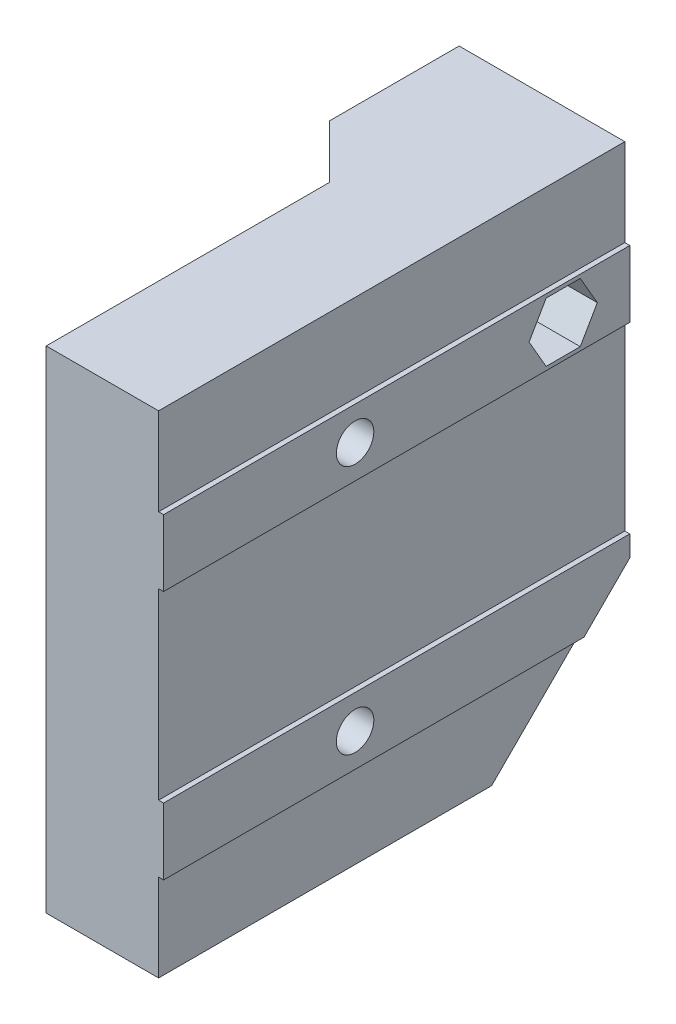
SolidWorks part; units mm, degrees
material "3D printed plastic"
ref_plane "Front Plane" through (0, 0, 0) normal (0, 0, 1) x (1, 0, 0)
ref_plane "Top Plane" through (0, 0, 0) normal (0, 1, 0) x (1, 0, 0)
ref_plane "Right Plane" through (0, 0, 0) normal (1, 0, 0) x (0, 0, -1)
sketch "Sketch1" plane through (0, 0, 0) normal (0, 0, 1) x (1, 0, 0)
  line L0 (0, 0) -> (15, 0) construction
  line L1 (-14, 32.5) -> (-1.5, 32.5)
  line L2 (-14, 32.5) -> (-14, -24.5)
  line L3 (-14, -24.5) -> (-1.5, -24.5)
  line L4 (15, 33.5) -> (15, 23)
  line L5 (1.5, -25.5) -> (15, -25.5)
  line L6 (1.5, -5.8095) -> (1.5, -25.5)
  line L7 (-1.5, 32.5) -> (-1.5, 5.8095)
  line L8 (15, -15) -> (15, -25.5)
  line L9 (1.5, 33.5) -> (1.5, 5.8095)
  line L10 (1.5, 33.5) -> (15, 33.5)
  line L11 (-1.5, -5.8095) -> (-1.5, -24.5)
  line L12 (-1.5, 5.8095) -> (1.5, 5.8095) construction
  line L13 (15, 23) -> (15.6, 23)
  line L14 (15.6, 19) -> (15, 19) construction
  line L15 (15, 15) -> (15.6, 15)
  line L16 (15.6, 23) -> (15.6, 15)
  line L17 (15, -7) -> (15.6, -7)
  line L18 (15, 15) -> (15, -7)
  line L19 (15, -15) -> (15.6, -15)
  line L20 (15.6, -7) -> (15.6, -15)
  line L21 (15.6, -11) -> (16.2538, -11) construction
  arc A0 (1.5, -5.8095) -> (1.5, 5.8095) centre (0, 0) ccw
  arc A1 (-1.5, 5.8095) -> (-1.5, -5.8095) centre (0, 0) ccw
  dimension "D1" = 59
  dimension "D2" = 12
  dimension "D3" = 15
  dimension "D4" = 29
  dimension "D5" = 3
  dimension "D6" = 8
  dimension "D7" = 30
  dimension "D8" = 0.6
  dimension "D9" = 25.5
  dimension "D10" = 1
  dimension "D11" = 1
extrude "Boss-Extrude1" add sketch "Sketch1" along normal mid plane 20
hole_wizard "CBORE for M5 Hex Socket Head Cap Screw1" positions "Sketch3" profile "Sketch2" counterbore size "M5" standard "DIN" end condition through all
sketch "Sketch3" plane through (-14, 0, 0) normal (-1, 0, 0) x (0, 0, 1)
  line L0 (0, 19) -> (0, -11) construction
  line L2 (0, 4) -> (-10, 4) construction
  line L3 (-10, 32.5) -> (-10, -24.5) construction
  line L5 (0, 4) -> (10, 4) construction
  line L7 (10, 32.5) -> (10, -24.5) construction
  point P0 (0, -11)
  point P2 (0, 19)
  dimension "D1" = 30
sketch "Sketch2" plane through (-14, -11, 0) normal (0, 1, 0) x (0, 0, 1)
  line L0 (0, 0) -> (0, 29.6)
  line L1 (0, 29.6) -> (2.25, 29.6)
  line L3 (2.25, 29.6) -> (2.25, 5.9)
  line L4 (2.25, 5.9) -> (5, 5.9)
  line L5 (5, 5.9) -> (5, 0)
  line L7 (5, 0) -> (0, 0)
  line L11 (0, -6.35) -> (0, 107.95) construction
  dimension "Thru Hole Dia." = 4.5
  dimension "Thru Hole Depth" = 29.6
  dimension "C'Bore Dia." = 10
  dimension "C'Bore Depth" = 5.9
sketch "Sketch4" plane through (0, 0, 10) normal (0, 0, 1) x (1, 0, 0)
  line L0 (1.5, 5.8095) -> (1.5, -5.8095)
  line L13 (15, -25.5) -> (15, -15)
  line L14 (15, -15) -> (15.6, -15)
  line L15 (15.6, -15) -> (15.6, -7)
  line L16 (15.6, -7) -> (15, -7)
  line L17 (15, -7) -> (15, 15)
  line L18 (15, 15) -> (15.6, 15)
  line L19 (15.6, 15) -> (15.6, 23)
  line L20 (15.6, 23) -> (15, 23)
  line L21 (15, 23) -> (15, 33.5)
  line L22 (15, 33.5) -> (1.5, 33.5)
  line L23 (1.5, 33.5) -> (1.5, 5.8095)
  line L24 (1.5, -5.8095) -> (1.5, -25.5)
  line L25 (1.5, -25.5) -> (15, -25.5)
  line L26 (15, -25.5) -> (15, -15)
  line L27 (15, -15) -> (15.6, -15)
  line L28 (15.6, -15) -> (15.6, -7)
  line L29 (15.6, -7) -> (15, -7)
  line L30 (15, -7) -> (15, 15)
  line L31 (15, 15) -> (15.6, 15)
  line L32 (15.6, 15) -> (15.6, 23)
  line L33 (15.6, 23) -> (15, 23)
  line L34 (15, 23) -> (15, 33.5)
  line L35 (15, 33.5) -> (1.5, 33.5)
  line L36 (1.5, 33.5) -> (1.5, 5.8095)
  line L37 (1.5, -5.8095) -> (1.5, -25.5)
  line L38 (1.5, -25.5) -> (15, -25.5)
  arc A1 (1.5, -5.8095) -> (1.5, 5.8095) centre (0, 0) ccw
  dimension "D1" = 0
extrude "Boss-Extrude2" add sketch "Sketch4" along normal blind 13
sketch "Sketch5" plane through (0, 0, -10) normal (0, 0, -1) x (-1, 0, 0)
  line L0 (-15, -25.5) -> (-1.5, -25.5)
  line L1 (-15, -15) -> (-15, -25.5)
  line L2 (-15.6, -7) -> (-15, -7)
  line L3 (-15.6, -7) -> (-15.6, -15)
  line L4 (-15.6, -15) -> (-15, -15)
  line L5 (-1.5, 5.8095) -> (-1.5, 33.5)
  line L13 (-15, -15) -> (-15, -25.5)
  line L14 (-15, -25.5) -> (-1.5, -25.5)
  line L15 (-1.5, -25.5) -> (-1.5, -5.8095)
  line L16 (-1.5, 5.8095) -> (-1.5, 33.5)
  line L17 (-1.5, 33.5) -> (-15, 33.5)
  line L18 (-15, 33.5) -> (-15, 23)
  line L19 (-15, 23) -> (-15.6, 23)
  line L20 (-15.6, 23) -> (-15.6, 15)
  line L21 (-15.6, 15) -> (-15, 15)
  line L22 (-15, 15) -> (-15, -7)
  line L23 (-15, -7) -> (-15.6, -7)
  line L24 (-15.6, -7) -> (-15.6, -15)
  line L25 (-15.6, -15) -> (-15, -15)
  line L29 (-1.5, -25.5) -> (-1.5, -5.8095)
  line L30 (-1.5, 33.5) -> (-15, 33.5)
  line L31 (-15, 33.5) -> (-15, 23)
  line L32 (-15, 23) -> (-15.6, 23)
  line L33 (-15.6, 23) -> (-15.6, 15)
  line L34 (-15.6, 15) -> (-15, 15)
  line L35 (-15, 15) -> (-15, -7)
  arc A0 (-1.5, 5.8095) -> (-1.5, -5.8095) centre (0, 0) ccw
  arc A1 (-1.5, 5.8095) -> (-1.5, -5.8095) centre (0, 0) ccw
  dimension "D1" = 0
extrude "Boss-Extrude3" add sketch "Sketch5" along normal blind 23
sketch "Sketch7" plane through (0, 33.5, 0) normal (0, 1, 0) x (1, 0, 0)
  line L0 (1.5, 33) -> (-4.9, 33)
  line L1 (-4.9, 33) -> (-4.9, 17.4)
  line L2 (-4.9, 17.4) -> (1.5, 11)
  line L3 (1.5, -23) -> (1.5, 33) construction
  line L4 (1.5, 11) -> (1.5, 33)
  dimension "D1" = 6.4
  dimension "D2" = 45
  dimension "D3" = 11
extrude "Boss-Extrude4" add sketch "Sketch7" against normal blind 27
sketch "Sketch8" plane through (-4.9, 0, 0) normal (-1, 0, 0) x (0, 0, 1)
  line L0 (-33, 33.5) -> (-17.4, 33.5) construction
  line L1 (-33, 6.5) -> (-33, 33.5) construction
  circle A0 centre (-25, 19) radius 2.1
  dimension "D1" = 14.5
  dimension "D2" = 8
  dimension "D3" = 4.2
extrude "Cut-Extrude1" cut sketch "Sketch8" against normal through all
chamfer "Chamfer1" distance 16 angle 45 1 edges at (8.25, -25.5, -33)
sketch "Sketch9" plane through (15.6, 0, 0) normal (1, 0, 0) x (0, 0, -1)
  line L1 (29.0992, 19) -> (27.0496, 22.55)
  line L2 (27.0496, 22.55) -> (22.9504, 22.55)
  line L3 (22.9504, 22.55) -> (20.9008, 19)
  line L4 (20.9008, 19) -> (22.9504, 15.45)
  line L5 (22.9504, 15.45) -> (27.0496, 15.45)
  line L6 (27.0496, 15.45) -> (29.0992, 19)
  circle A0 centre (25, 19) radius 3.55 construction
  dimension "D1" = 7.1
extrude "Cut-Extrude2" cut sketch "Sketch9" against normal blind 6
sketch "Sketch10" plane through (-4.9, 0, 0) normal (-1, 0, 0) x (0, 0, 1)
  circle A0 centre (-25, 19) radius 5
  circle A1 centre (-25, 19) radius 2.1
  circle A2 centre (-25, 19) radius 2.1 construction
  dimension "D1" = 10
extrude "Boss-Extrude5" add sketch "Sketch10" along normal blind 0.7
chamfer "Chamfer2" distance 1 angle 45 1 edges at (-5.6, 19, -20)
delete or keep bodies "Body-Delete1" type delete bodies bodies 103
